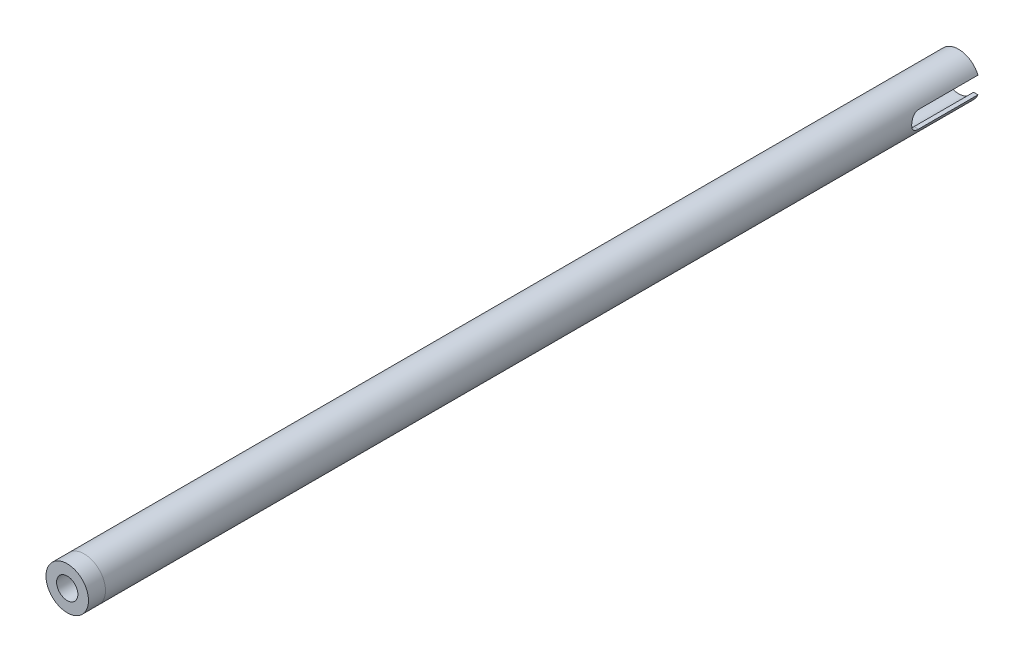
SolidWorks part; units mm, degrees
material "AISI 4130 Steel, normalized at 870C"
ref_plane "Front Plane" through (0, 0, 0) normal (0, 0, 1) x (1, 0, 0)
ref_plane "Top Plane" through (0, 0, 0) normal (0, 1, 0) x (1, 0, 0)
ref_plane "Right Plane" through (0, 0, 0) normal (1, 0, 0) x (0, 0, -1)
sketch "Axis" plane through (0, 0, 0) normal (0, 1, 0) x (1, 0, 0)
  line L0 (0, 0) -> (0, 332.6617) construction
  line L1 (0, 0) -> (0, -28.575) construction
  line L2 (0, 332.6617) -> (-7.9375, 332.6617) construction
  line L3 (0, 361.4136) -> (-10.3187, 324.0362) construction
  dimension "D1" = 28.575
  dimension "D2" = 7.9375
sketch "Sketch1" plane through (0, 0, 0) normal (0, 0, 1) x (1, 0, 0)
  line L0 (-7.9375, 0) -> (7.9375, 0) construction
  line L1 (-7.2748, 3.175) -> (7.2748, 3.175)
  line L2 (-7.2748, -3.175) -> (7.2748, -3.175)
  circle A0 centre (0, 0) radius 7.9375
  circle A1 centre (0, 0) radius 6.4643
  circle A2 centre (0, 0) radius 3.9688
  dimension "D1" = 15.875
  dimension "D3" = 7.9375
  dimension "D2" = 1.4732
  dimension "D4" = 6.35
extrude "Threaded insert 1-1" add sketch "Sketch1" against normal blind 6.35 contours A2 L1 A1 | A1 L1 A0 | A2 L0 A1 L1 | A1 L0 A0 L1 | L0 A1 L2 A0 | L0 A2 L2 A1 | A2 L2 A1 | A1 L2 A0 | L0 A1 L2 A2 | L0 A0 L2 A1 | A0 L0 A1 L1 | A1 L0 A2 L1 region at (4.8156, 1.6537, 0) region at (4.8156, -1.6537, 0) region at (6.9501, 1.6161, 0) region at (6.9501, -1.6161, 0) region at (-4.8156, -1.6537, 0) region at (-4.8156, 1.6537, 0) region at (0, 4.6361, 0) region at (0, -4.6361, 0) region at (0, 6.6174, 0) region at (6.4528, -3.3281, 0) region at (-6.9501, -1.6161, 0) region at (-6.9501, 1.6161, 0)
extrude "Threaded insert 1-2" add sketch "Sketch1<3>" against normal blind 9.525 from surface contours A2 L1 A1 | A2 L0 A1 L1 | L0 A2 L2 A1 | A2 L2 A1 | L0 A1 L2 A2 | A1 L0 A2 L1 region at (4.8156, 1.6537, 0) region at (4.8156, -1.6537, 0) region at (-4.8156, -1.6537, 0) region at (-4.8156, 1.6537, 0) region at (0, 4.6361, 0) region at (0, -4.6361, 0) starting at face at (7.9375, 0, -6.35)
sketch "Sketch1<3>" plane through (0, 0, 0) normal (0, 0, 1) x (1, 0, 0) same geometry as "Sketch1"
extrude "A-arm tube" add sketch "Sketch1<4>" against normal up to vertex (332.6617 mm away) from surface separate body contours A1 L1 A0 | A1 L0 A0 L1 | L0 A1 L2 A0 | A1 L2 A0 | L0 A0 L2 A1 | A0 L0 A1 L1 region at (6.9501, 1.6161, 0) region at (6.9501, -1.6161, 0) region at (0, 6.6174, 0) region at (6.4528, -3.3281, 0) region at (-6.9501, -1.6161, 0) region at (-6.9501, 1.6161, 0) up to point (0, 0, -332.6617) starting at face at (6.4643, 0, -6.35)
sketch "Sketch1<4>" plane through (0, 0, 0) normal (0, 0, 1) x (1, 0, 0) same geometry as "Sketch1"
extrude "Apex slot" cut sketch "Sketch1<5>" along normal blind 25.4 from surface contours A0 L0 A1 L1 | L0 A0 L2 A1 | A1 L0 A0 L1 | L0 A1 L2 A0 region at (6.9501, 1.6161, 0) region at (6.9501, -1.6161, 0) region at (-6.9501, -1.6161, 0) region at (-6.9501, 1.6161, 0) starting at face at (6.4643, 0, -332.6617)
sketch "Sketch1<5>" plane through (0, 0, 0) normal (0, 0, 1) x (1, 0, 0) same geometry as "Sketch1"
fillet "Fillet1" radius 3.175 4 edges at (-6.4528, 3.175, -307.2617) (-6.4528, -3.175, -307.2617) (6.4528, -3.175, -307.2617) (6.4528, 3.175, -307.2617)
equation "\"tube diameter\"= 5 / 8"
equation "\"tube thickness\"= .058"
equation "\"apex thickness\"= .25"
equation "\"tube slot\"= 1"
equation "\"D1@Sketch1\"=\"tube diameter\""
equation "\"D2@Sketch1\"=\"tube thickness\""
equation "\"threaded insert hole\"= .3125"
equation "\"D3@Sketch1\"=\"threaded insert hole\""
equation "\"D4@Sketch1\"=\"apex thickness\""
equation "\"D1@Apex slot\" = \"tube slot\""
equation "\"D1@Fillet1\"=\"apex thickness\"/2"
equation "\"D2@Axis\"=\"tube diameter\"/2"
